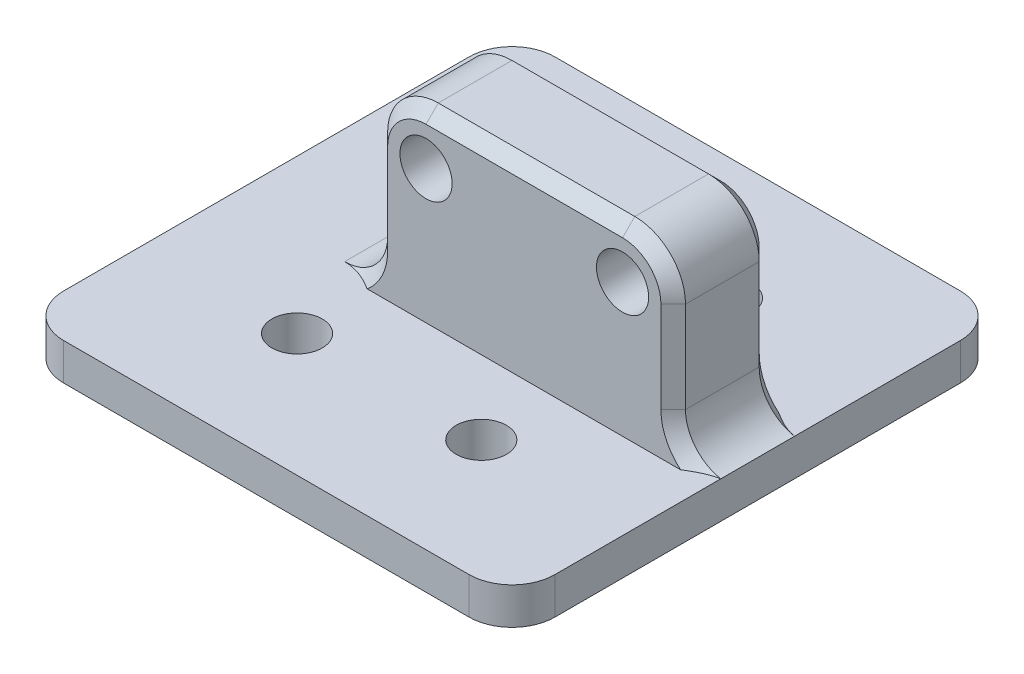
SolidWorks part; units mm, degrees
ref_plane "Front Plane" through (0, 0, 0) normal (0, 0, 1) x (1, 0, 0)
ref_plane "Top Plane" through (0, 0, 0) normal (0, 1, 0) x (1, 0, 0)
ref_plane "Right Plane" through (0, 0, 0) normal (1, 0, 0) x (0, 0, -1)
sketch "Sketch1" plane through (0, 0, 0) normal (0, 1, 0) x (1, 0, 0)
  line L1 (-20, -20) -> (20, -20)
  line L2 (-20, -20) -> (-20, 20)
  line L3 (-20, 20) -> (20, 20)
  line L4 (20, -20) -> (20, 20)
  line L5 (-20, -20) -> (20, 20) construction
  line L6 (-20, 20) -> (20, -20) construction
  point P0 (0, 0)
  line B0 (-7.5, -10) -> (7.5, -10) construction
  line B1 (-7.5, -10) -> (-7.5, 10) construction
  line B2 (-7.5, 10) -> (7.5, 10) construction
  line B3 (7.5, -10) -> (7.5, 10) construction
  circle B4 centre (-7.5, 10) radius 2.05
  circle B5 centre (7.5, 10) radius 2.05
  circle B6 centre (-7.5, -10) radius 2.05
  circle B7 centre (7.5, -10) radius 2.05
  dimension "D1" = 40
  dimension "D2" = 40
sketch_block_instance "Block1-1"
sketch_block "Block1" parameters "D1"=4.1, "D2"=20, "D3"=15
extrude "Boss-Extrude1" add sketch "Sketch1" along normal blind 3 contours B5 | L1 L4 L3 L2 B7 B6 B5 B4 | L2 L1 L4 L3 region at (0, 0, 0) region at (7.5, 0, -10)
fillet "Fillet1" radius 3.5 4 edges at (-20, 1.5, 20) (20, 1.5, -20) (-20, 1.5, -20) (20, 1.5, 20)
sketch "Sketch2" plane through (0, 0, 0) normal (0, 0, 1) x (1, 0, 0)
  line L0 (5, 0) -> (17.125, 0)
  line L1 (-16.5, 0) -> (16.5, 0) construction
  line L2 (17.125, 0) -> (17.125, 13.875)
  line L3 (13, 18) -> (-3, 18)
  line L4 (-7.125, 13.875) -> (-7.125, 0)
  line L5 (-7.125, 0) -> (5, 0)
  line L6 (-3, 13.875) -> (13, 13.875) construction
  arc A1 (-3, 18) -> (-7.125, 13.875) centre (-3, 13.875) ccw
  arc A2 (13, 18) -> (17.125, 13.875) centre (13, 13.875) cw
  circle A3 centre (-3, 13.875) radius 2.125
  circle A4 centre (13, 13.875) radius 2.125
  point P11 (5, 18)
  point P16 (5, 13.875)
  dimension "D2" = 4.25
  dimension "D3" = 2
  dimension "D1" = 16
  dimension "D4" = 18
  dimension "D5" = 5
extrude "Boss-Extrude2" add sketch "Sketch2" along normal mid plane 8
fillet "Fillet2" radius 3.5 2 edges at (17.125, 3, 0) (-7.125, 3, 0)
chamfer "Chamfer1" distance 1 angle 45 14 edges at (17.9382, 4.2007, -4) (-8.1501, 4.0251, -4) (17.125, 10.1594, -4) (-7.125, 10.1875, -4) (15.9168, 16.7918, -4) (-5.9168, 16.7918, -4) (5, 18, -4) (17.9382, 4.2007, 4) (-8.1501, 4.0251, 4) (17.125, 10.1594, 4) (-7.125, 10.1875, 4) (15.9168, 16.7918, 4) (-5.9168, 16.7918, 4) (5, 18, 4)
extrude "Cut-Extrude2" cut sketch "Sketch1<3>" against normal through all and the other way through all contours B4 | B5 | B7 | B6 region at (-7.5, 0, -10) region at (7.5, 0, -10) region at (-7.5, 0, 10) region at (7.5, 0, 10)
sketch "Sketch1<3>" plane through (0, 0, 0) normal (0, 1, 0) x (1, 0, 0) same geometry as "Sketch1"
